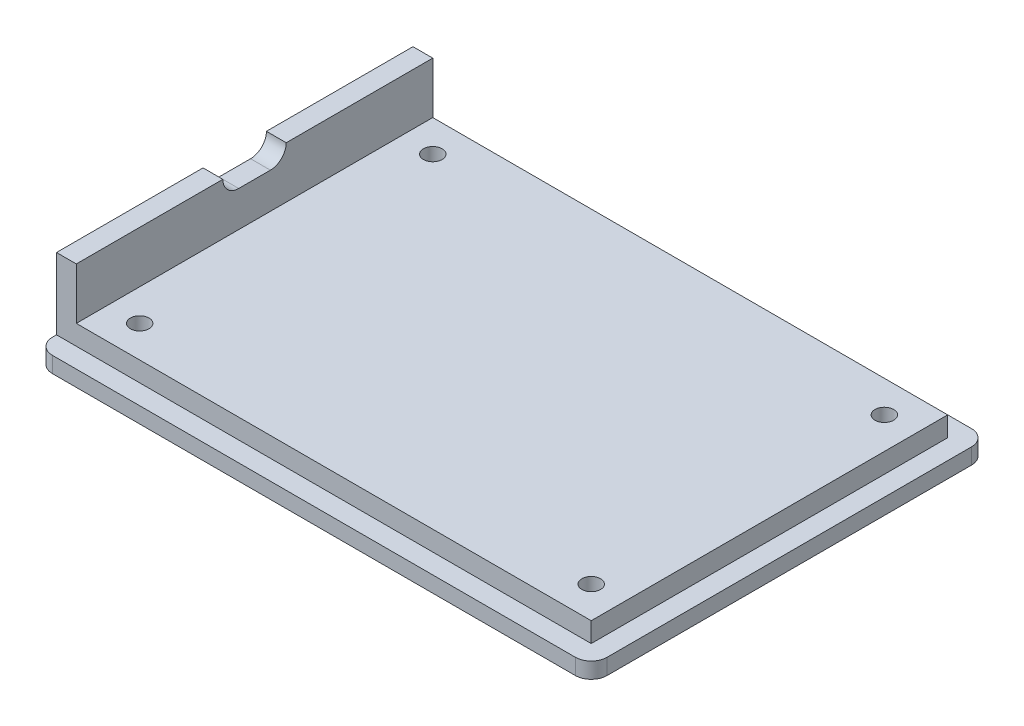
SolidWorks part; units mm, degrees
ref_plane "Front Plane" through (0, 0, 0) normal (0, 0, 1) x (1, 0, 0)
ref_plane "Top Plane" through (0, 0, 0) normal (0, 1, 0) x (1, 0, 0)
ref_plane "Right Plane" through (0, 0, 0) normal (1, 0, 0) x (0, 0, -1)
sketch "Sketch1" plane through (0, 0, 0) normal (0, 1, 0) x (1, 0, 0)
  line L0 (-44.45, 31.75) -> (44.45, 31.75)
  line L1 (-41.275, -28.575) -> (41.275, -28.575)
  line L2 (-41.275, -28.575) -> (-41.275, 28.575)
  line L3 (-41.275, 28.575) -> (41.275, 28.575)
  line L4 (41.275, -28.575) -> (41.275, 28.575)
  line L5 (-41.275, -28.575) -> (41.275, 28.575) construction
  line L6 (-41.275, 28.575) -> (41.275, -28.575) construction
  line L7 (44.45, -31.75) -> (44.45, 31.75)
  line L8 (-44.45, -31.75) -> (44.45, -31.75)
  line L9 (-44.45, -31.75) -> (-44.45, 31.75)
  point P0 (0, 0)
  dimension "Width" = 57.15
  dimension "Length" = 82.55
  dimension "Thick" = 3.175
extrude "Boss-Extrude2" add sketch "Sketch1" along normal blind 5.715 contours L2 L1 L4 L3
extrude "Top" add sketch "Sketch1<7>" along normal blind 2.54
sketch "Sketch1<7>" plane through (0, 0, 0) normal (0, 1, 0) x (1, 0, 0) same geometry as "Sketch1"
sketch "Sketch3" plane through (-44.45, 0, 0) normal (-1, 0, 0) x (0, 0, 1)
  line L0 (-28.575, 2.54) -> (28.575, 2.54)
  line L1 (28.575, 2.54) -> (28.575, 13.97)
  line L2 (28.575, 13.97) -> (5.08, 13.97)
  line L3 (5.08, 13.97) -> (5.08, 11.43)
  line L4 (5.08, 11.43) -> (-5.08, 11.43)
  line L5 (-5.08, 11.43) -> (-5.08, 13.97)
  line L6 (-5.08, 13.97) -> (-28.575, 13.97)
  line L7 (-28.575, 13.97) -> (-28.575, 2.54)
  line L8 (0, 11.43) -> (0, 0) construction
  dimension "D1" = 11.43
  dimension "D2" = 10.16
  dimension "D3" = 2.54
extrude "FrontLip" add sketch "Sketch3" against normal up to surface (3.175 mm away) up to face at (-41.275, 4.1275, 0)
sketch "Sketch4" plane through (0, 5.715, 0) normal (0, 1, 0) x (1, 0, 0)
  line L0 (-41.275, 0) -> (41.275, 0) construction
  line L1 (-31.115, 18.415) -> (-41.275, 18.415) construction
  line L2 (-31.115, 18.415) -> (-31.115, 28.575) construction
  line L3 (-31.115, 28.575) -> (-41.275, 28.575) construction
  line L4 (-41.275, 18.415) -> (-41.275, 28.575) construction
  line L5 (-31.115, 18.415) -> (-41.275, 28.575) construction
  line L6 (-31.115, 28.575) -> (-41.275, 18.415) construction
  line L7 (31.115, 18.415) -> (41.275, 18.415) construction
  line L8 (31.115, 18.415) -> (31.115, 28.575) construction
  line L9 (31.115, 28.575) -> (41.275, 28.575) construction
  line L10 (41.275, 18.415) -> (41.275, 28.575) construction
  line L11 (31.115, 18.415) -> (41.275, 28.575) construction
  line L12 (31.115, 28.575) -> (41.275, 18.415) construction
  line L13 (-41.275, 5.08) -> (-41.275, -5.08) construction
  line L14 (41.275, -28.575) -> (41.275, 28.575) construction
  circle A0 centre (-36.195, 23.495) radius 1.5
  circle A1 centre (36.195, 23.495) radius 1.5
  circle A2 centre (36.195, -23.495) radius 1.5
  circle A3 centre (-36.195, -23.495) radius 1.5
  point P0 (-36.195, 23.495)
  point P6 (36.195, 23.495)
  dimension "D2" = 3
  dimension "D1" = 10.16
extrude "M3ScrewHole" cut sketch "Sketch4" against normal blind 13.208
fillet "Fillet1" radius 2.54 6 edges at (-42.8625, 11.43, -5.08) (-42.8625, 11.43, 5.08) (44.45, 1.27, 31.75) (44.45, 1.27, -31.75) (-44.45, 1.27, 31.75) (-44.45, 1.27, -31.75)
sketch "Sketch5" plane through (0, 0, 0) normal (0, -1, 0) x (1, 0, 0)
  circle A0 centre (-36.195, 23.495) radius 3.5
  circle A1 centre (-36.195, -23.495) radius 3.5
  circle A2 centre (36.195, -23.495) radius 3.5
  circle A3 centre (36.195, 23.495) radius 3.5
  dimension "D1" = 7
extrude "ScrewHeadHole" cut sketch "Sketch5" against normal blind 3.175
